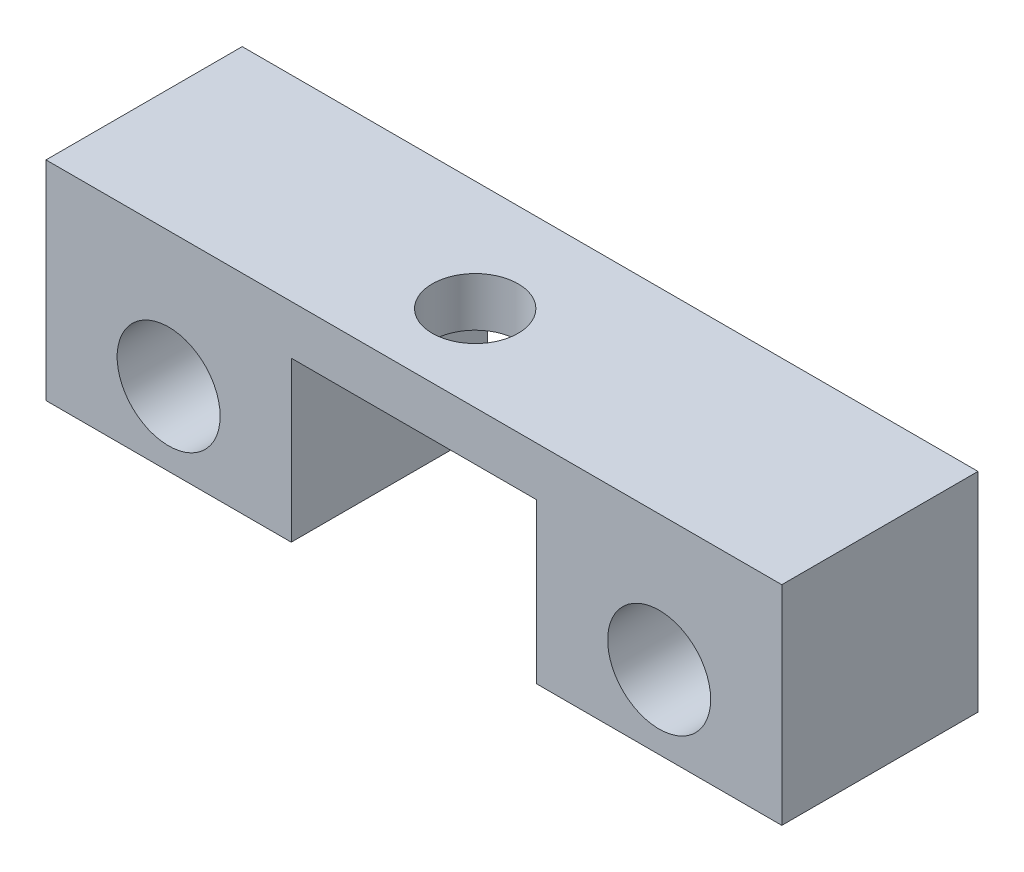
SolidWorks part; units mm, degrees
ref_plane "Front Plane" through (0, 0, 0) normal (0, 0, 1) x (1, 0, 0)
ref_plane "Top Plane" through (0, 0, 0) normal (0, 1, 0) x (1, 0, 0)
ref_plane "Right Plane" through (0, 0, 0) normal (1, 0, 0) x (0, 0, -1)
sketch "Sketch1" plane through (0, 0, 0) normal (0, 1, 0) x (1, 0, 0)
  line L0 (-1, -0.5) -> (-1, -4) construction
  line L5 (-15, 4) -> (15, 4)
  line L6 (-15, 4) -> (-15, -4)
  line L7 (-15, -4) -> (15, -4)
  line L8 (15, 4) -> (15, -4)
  line L9 (-15, 4) -> (15, -4) construction
  line L10 (-15, -4) -> (15, 4) construction
  line L11 (-1, 0) -> (0, 0) construction
  circle A0 centre (-1, -0.5) radius 1.75
  point P0 (0, 0)
  point P11 (0, 0)
  point P12 (0, 0)
  point P13 (-2.7771, 0)
  point P14 (-2.575, 0)
  dimension "D3" = 3.5
  dimension "D1" = 30
  dimension "D2" = 8
  dimension "D4" = 3.5
  dimension "D5" = 1
extrude "Boss-Extrude1" add sketch "Sketch1" along normal blind 2
sketch "Sketch2" plane through (0, 0, 4) normal (0, 0, 1) x (1, 0, 0)
  line L0 (-10, -3.5) -> (10, -3.5) construction
  line L1 (-15, 0) -> (-5, 0)
  line L2 (-15, 0) -> (-15, -6.5)
  line L3 (-15, -6.5) -> (-5, -6.5)
  line L4 (-5, 0) -> (-5, -6.5)
  line L5 (15, 0) -> (5, 0)
  line L6 (15, 0) -> (15, -6.5)
  line L7 (15, -6.5) -> (5, -6.5)
  line L8 (5, 0) -> (5, -6.5)
  line L10 (-15, 2) -> (15, 2) construction
  line L11 (-15, 0) -> (15, 0) construction
  circle A0 centre (-10, -3.5) radius 2.1
  circle A1 centre (10, -3.5) radius 2.1
  point P12 (-10, 0)
  point P13 (10, 0)
  point P17 (0, -3.5)
  point P22 (0, 0)
  dimension "D1" = 4.2
  dimension "D2" = 4.2
  dimension "D3" = 5.5
  dimension "D4" = 6.5
  dimension "D5" = 20
extrude "Boss-Extrude2" add sketch "Sketch2" against normal up to surface (8 mm away) up to face at (0, 1, -4)
sketch "Sketch3" plane through (0, 0, 0) normal (0, -1, 0) x (1, 0, 0)
  line L1 (-2.7321, -2.5) -> (0.7321, -2.5) construction
  line L2 (0.7321, -2.5) -> (2.4641, 0.5) construction
  line L3 (2.4641, 0.5) -> (0.7321, 3.5) construction
  line L4 (0.7321, 3.5) -> (-2.7321, 3.5) construction
  line L5 (-2.7321, 3.5) -> (-4.4641, 0.5) construction
  line L6 (-4.4641, 0.5) -> (-2.7321, -2.5) construction
  circle A0 centre (-1, 0.5) radius 3 construction
  dimension "D1" = 6
sketch "Sketch4" plane through (0, 0, -4) normal (0, 0, -1) x (-1, 0, 0)
  line L8 (-15, 2) -> (-15, -6.5)
  line L9 (-15, -6.5) -> (-5, -6.5)
  line L10 (-5, -6.5) -> (-5, 0)
  line L11 (-5, 0) -> (5, 0)
  line L12 (5, 0) -> (5, -6.5)
  line L13 (5, -6.5) -> (15, -6.5)
  line L14 (15, -6.5) -> (15, 2)
  line L15 (15, 2) -> (-15, 2)
  line L16 (-15, 2) -> (-15, -6.5)
  line L17 (-15, -6.5) -> (-5, -6.5)
  line L18 (-5, -6.5) -> (-5, 0)
  line L19 (-5, 0) -> (5, 0)
  line L20 (5, 0) -> (5, -6.5)
  line L21 (5, -6.5) -> (15, -6.5)
  line L22 (15, -6.5) -> (15, 2)
  line L23 (15, 2) -> (-15, 2)
  dimension "D1" = 0
extrude "Boss-Extrude3" add sketch "Sketch4" against normal offset from surface (2 mm away) 6 up to face at (0, -2.75, 4)
